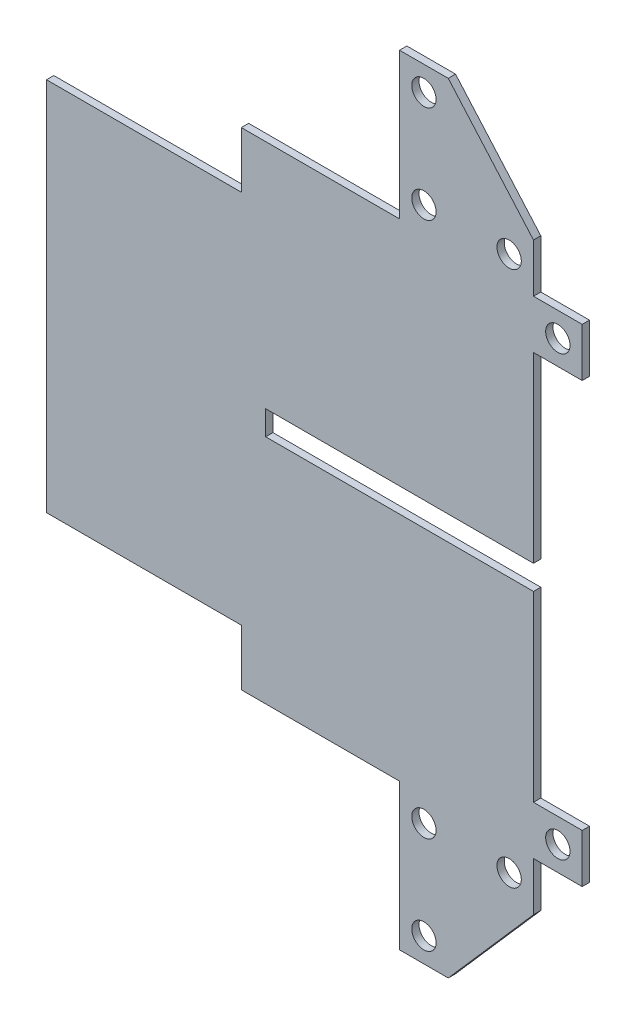
SolidWorks part; units mm, degrees
ref_plane "Plan de face" through (0, 0, 0) normal (0, 0, 1) x (1, 0, 0)
ref_plane "Plan de dessus" through (0, 0, 0) normal (0, 1, 0) x (1, 0, 0)
ref_plane "Plan de droite" through (0, 0, 0) normal (1, 0, 0) x (0, 0, -1)
sketch "Esquisse1" plane through (0, 0, 0) normal (0, 0, 1) x (1, 0, 0)
  line L0 (200, 80) -> (220, 100) construction
  line L1 (0, 100) -> (200, 100)
  line L2 (0, 100) -> (0, 0)
  line L3 (0, 0) -> (200, 0)
  line L4 (200, 100) -> (200, 0)
  line L5 (0, 100) -> (55, 100)
  line L7 (0, 100) -> (80, 100)
  line L8 (0, 100) -> (0, 77)
  line L9 (200, 100) -> (145, 100)
  line L10 (200, 100) -> (200, 160)
  line L11 (200, 160) -> (145, 160)
  line L12 (145, 100) -> (145, 160)
  line L13 (200, 0) -> (90, 0)
  line L14 (200, 0) -> (200, 5)
  line L15 (200, 5) -> (90, 5)
  line L16 (90, 0) -> (90, 5)
  line L17 (200, 100) -> (220, 100)
  line L18 (200, 100) -> (200, 80)
  line L19 (200, 80) -> (220, 80)
  line L20 (220, 100) -> (220, 80)
  line L21 (200, 120) -> (180, 120) construction
  line L22 (180, 120) -> (180, 100) construction
  line L23 (180, 120) -> (200, 100) construction
  line L24 (0, 77) -> (80, 77)
  line L25 (80, 100) -> (80, 77)
  line L32 (165, 160) -> (165, 100) construction
  line L33 (145, 140) -> (165, 140) construction
  line L34 (165, 120) -> (145, 120) construction
  line L35 (145, 160) -> (165, 140) construction
  line L36 (145, 120) -> (165, 100) construction
  line L38 (165, 160) -> (200, 120)
  line L39 (220, 100) -> (200, 120)
  line L40 (200, 5) -> (220, 80)
  circle A0 centre (210, 90) radius 5
  circle A1 centre (190, 110) radius 5
  circle A5 centre (155, 150) radius 5
  circle A6 centre (155, 110) radius 5
  point P19 (210, 90)
  point P24 (190, 110)
  point P56 (155, 150)
  point P58 (155, 110)
  dimension "D9" = 10
  dimension "D10" = 10
  dimension "D21" = 10
  dimension "D22" = 10
  dimension "D1" = 200
  dimension "D2" = 100
  dimension "D3" = 80
  dimension "D4" = 23
  dimension "D5" = 110
  dimension "D6" = 5
  dimension "D7" = 20
  dimension "D8" = 20
  dimension "D11" = 20
  dimension "D12" = 20
  dimension "D20" = 20
extrude "Boss.-Extru.1" add sketch "Esquisse1" along normal blind 3 contours L24 L1 | L3 L16 L15 L4 L1 L2 | L38 L11 L12 L1 L10 A6 A5 A1 | L20 L17 L4 L19 A0 region at (104.8637, 47.4608, 0) region at (168.3937, 125.73, 0) region at (210, 99.7172, 0)
mirror "Symétrie1" about plane through (0, 0, 3) normal (0, 1, 0) of "Boss.-Extru.1"
